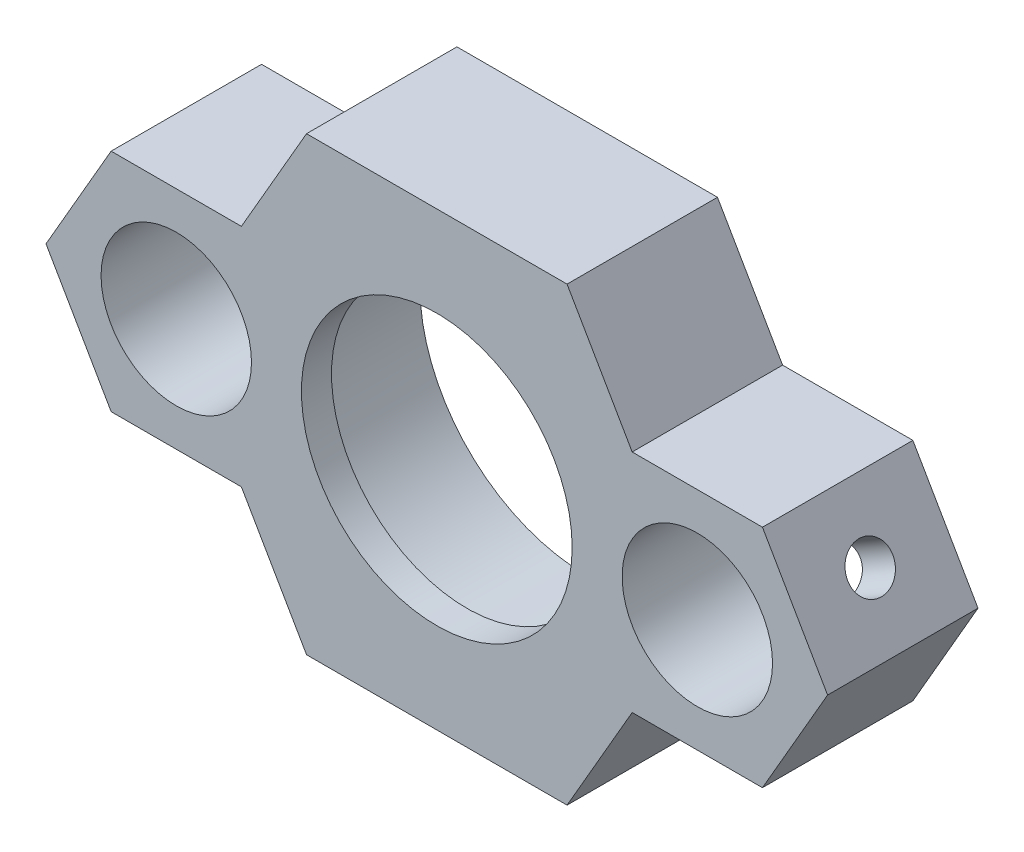
SolidWorks part; units mm, degrees
ref_plane "Front Plane" through (0, 0, 0) normal (0, 0, 1) x (1, 0, 0)
ref_plane "Top Plane" through (0, 0, 0) normal (0, 1, 0) x (1, 0, 0)
ref_plane "Right Plane" through (0, 0, 0) normal (1, 0, 0) x (0, 0, -1)
sketch "Sketch3" plane through (0, 0, 0) normal (0, 0, 1) x (1, 0, 0)
  line L0 (-15, 0) -> (17.3205, 0) construction
  line L1 (17.3205, 0) -> (14.8205, 4.3301) construction
  line L2 (8.6603, 15) -> (-8.6603, 15)
  line L3 (-8.6603, 15) -> (-12.9904, 7.5)
  line L4 (-12.9904, -7.5) -> (-8.6603, -15)
  line L5 (-8.6603, -15) -> (8.6603, -15)
  line L6 (8.6603, -15) -> (12.9904, -7.5)
  line L7 (0, 15) -> (0, -15) construction
  line L8 (25.9808, 0) -> (21.6506, 7.5)
  line L9 (21.6506, 7.5) -> (12.9904, 7.5)
  line L10 (10.8253, 3.75) -> (10.6036, 3.3659) construction
  line L11 (10.6036, -3.3659) -> (10.8253, -3.75) construction
  line L12 (12.9904, -7.5) -> (21.6506, -7.5)
  line L13 (21.6506, -7.5) -> (25.9808, 0)
  line L14 (-21.6506, -7.5) -> (-25.9808, 0)
  line L15 (-12.9904, -7.5) -> (-21.6506, -7.5)
  line L16 (-10.6036, -3.3659) -> (-12.9904, -7.5) construction
  line L17 (-10.6036, 3.3659) -> (-8.6603, 0) construction
  line L18 (-21.6506, 7.5) -> (-12.9904, 7.5)
  line L19 (-25.9808, 0) -> (-21.6506, 7.5)
  line L20 (-14.8205, 4.3301) -> (-17.3205, 0) construction
  line L21 (-17.3205, 0) -> (-15, 0) construction
  line L22 (-17.3205, 0) -> (-14.8205, -4.3301) construction
  line L23 (-12.9904, 7.5) -> (-14.8205, 4.3301) construction
  line L24 (-14.8205, -4.3301) -> (-12.9904, -7.5) construction
  line L25 (14.8205, 4.3301) -> (13.5705, 6.4952) construction
  line L26 (12.9904, 7.5) -> (8.6603, 15)
  line L27 (14.8205, -4.3301) -> (17.3205, 0) construction
  line L28 (13.5705, -6.4952) -> (14.8205, -4.3301) construction
  line L29 (12.9904, -7.5) -> (13.5705, -6.4952) construction
  line L30 (13.5705, 6.4952) -> (12.9904, 7.5) construction
  line L31 (-12.9904, 7.5) -> (-10.6036, 3.3659) construction
  line L32 (-8.6603, 0) -> (-10.6036, -3.3659) construction
  line L33 (10.8253, -3.75) -> (12.9904, -7.5) construction
  line L34 (8.6603, 0) -> (10.6036, -3.3659) construction
  line L35 (10.6036, 3.3659) -> (8.6603, 0) construction
  line L36 (12.9904, 7.5) -> (10.8253, 3.75) construction
  circle A0 centre (0, 0) radius 11.125
  circle A1 centre (0, 0) radius 15 construction
  circle A2 centre (17.3205, 0) radius 5
  circle A3 centre (17.3205, 0) radius 7.5 construction
  circle A4 centre (-17.3205, 0) radius 5
  dimension "D1" = 22.25
  dimension "D3" = 10
  dimension "D2" = 30
  dimension "D4" = 15
extrude "Boss-Extrude1" add sketch "Sketch3" along normal blind 8
sketch "Sketch4" plane through (0, 0, 8) normal (0, 0, 1) x (1, 0, 0)
  line L0 (-8.6603, 15) -> (-12.9904, 7.5)
  line L1 (-12.9904, 7.5) -> (-21.6506, 7.5)
  line L2 (-21.6506, 7.5) -> (-25.9808, 0)
  line L3 (-25.9808, 0) -> (-21.6506, -7.5)
  line L4 (-21.6506, -7.5) -> (-12.9904, -7.5)
  line L5 (-12.9904, -7.5) -> (-8.6603, -15)
  line L6 (-8.6603, -15) -> (8.6603, -15)
  line L7 (8.6603, -15) -> (12.9904, -7.5)
  line L8 (12.9904, -7.5) -> (21.6506, -7.5)
  line L9 (21.6506, -7.5) -> (25.9808, 0)
  line L10 (25.9808, 0) -> (21.6506, 7.5)
  line L11 (21.6506, 7.5) -> (12.9904, 7.5)
  line L12 (12.9904, 7.5) -> (8.6603, 15)
  line L13 (8.6603, 15) -> (-8.6603, 15)
  circle A0 centre (0, 0) radius 9
  circle A1 centre (-17.3205, 0) radius 5
  circle A2 centre (17.3205, 0) radius 5
  circle A3 centre (-17.3205, 0) radius 5 construction
  circle A4 centre (17.3205, 0) radius 5 construction
  dimension "D1" = 18
extrude "Boss-Extrude3" add sketch "Sketch4" along normal blind 2
sketch "Sketch5" plane through (-19.4856, 11.25, 0) normal (-0.866, 0.5, 0) x (0, 0, 1)
  line L0 (5, -4.3301) -> (5, -12.9904) construction
  line L1 (10, -4.3301) -> (0, -4.3301) construction
  line L2 (10, -12.9904) -> (0, -12.9904) construction
  line L3 (0, -8.6603) -> (10, -8.6603) construction
  line L4 (0, -4.3301) -> (0, -12.9904) construction
  circle A0 centre (5, -8.6603) radius 1.5
  dimension "D1" = 3
extrude "Cut-Extrude1" cut sketch "Sketch5" against normal up to surface (2.7303 mm away) up to face at (-22.3205, 0, 0)
sketch "Sketch6" plane through (19.4856, 11.25, 0) normal (0.866, 0.5, 0) x (0, 0, -1)
  line L0 (-5, -4.3301) -> (-5, -12.9904) construction
  line L1 (-10, -4.3301) -> (0, -4.3301) construction
  line L2 (-10, -12.9904) -> (0, -12.9904) construction
  line L3 (-10, -8.6603) -> (0, -8.6603) construction
  line L4 (-10, -12.9904) -> (-10, -4.3301) construction
  line L5 (0, -12.9904) -> (0, -4.3301) construction
  circle A0 centre (-5, -8.6603) radius 1.5
  dimension "D1" = 3
extrude "Cut-Extrude2" cut sketch "Sketch6" against normal up to surface (2.7303 mm away) up to face at (22.3205, 0, 0)
